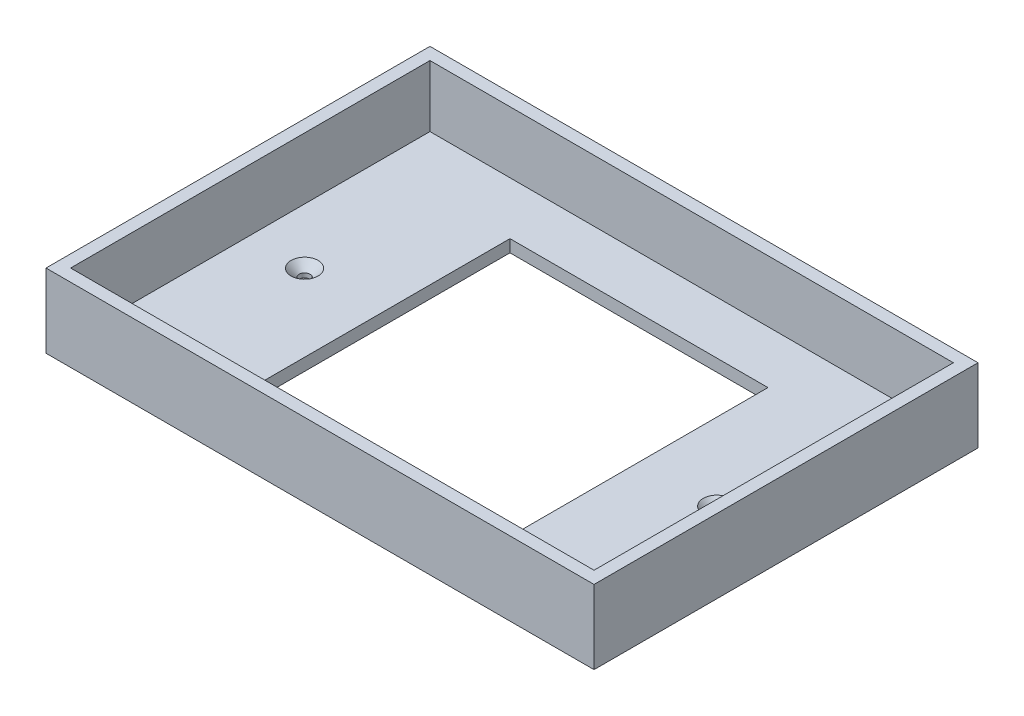
SolidWorks part; units mm, degrees
ref_plane "Front Plane" through (0, 0, 0) normal (0, 0, 1) x (1, 0, 0)
ref_plane "Top Plane" through (0, 0, 0) normal (0, 1, 0) x (1, 0, 0)
ref_plane "Right Plane" through (0, 0, 0) normal (1, 0, 0) x (0, 0, -1)
sketch "Sketch1" plane through (0, 0, 0) normal (0, 1, 0) x (1, 0, 0)
  line L0 (-44.545, -31.21) -> (-44.545, 31.21)
  line L1 (-42.545, -29.21) -> (42.545, -29.21)
  line L2 (-42.545, -29.21) -> (-42.545, 29.21)
  line L3 (-42.545, 29.21) -> (42.545, 29.21)
  line L4 (42.545, -29.21) -> (42.545, 29.21)
  line L5 (-42.545, -29.21) -> (42.545, 29.21) construction
  line L6 (-42.545, 29.21) -> (42.545, -29.21) construction
  line L7 (-44.545, 31.21) -> (44.545, 31.21)
  line L8 (44.545, -31.21) -> (44.545, 31.21)
  line L9 (-44.545, -31.21) -> (44.545, -31.21)
  point P0 (0, 0)
  dimension "D1" = 58.42
  dimension "D2" = 85.09
  dimension "D3" = 2
extrude "Boss-Extrude1" add sketch "Sketch1" against normal blind 2 contours L1 L4 L3 L2 | L0 L9 L8 L7 L4 L1 L2 L3 region at (-43.4572, 0, 0) region at (0, 0, 0)
extrude "Boss-Extrude2" add sketch "Sketch1<3>" along normal blind 10
sketch "Sketch1<3>" plane through (0, 0, 0) normal (0, 1, 0) x (1, 0, 0) same geometry as "Sketch1"
hole_wizard "CSK for M2 Flat Head Machine Screw1" positions "Sketch4" profile "Sketch6" countersink size "M2" standard "ANSI Metric"
sketch "Sketch4" plane through (0, 0, 0) normal (0, 1, 0) x (1, 0, 0)
  circle A0 centre (-33.5, -0.2189) radius 0.8 construction
  circle A1 centre (33.5, -0.2189) radius 0.8 construction
  point P156 (-33.5, -0.2189)
  point P158 (33.5, -0.2189)
  point P161 (0, 0)
  point P164 (0, 0)
sketch "Sketch6" plane through (-33.5, 0, 0.2189) normal (1, 0, 0) x (0, 0, 1)
  line L0 (0, 0) -> (0, 10.4468)
  line L1 (0, 10.4468) -> (0.9, 9.906)
  line L2 (0.9, 9.906) -> (0.9, 1.3)
  line L3 (0.9, 1.3) -> (2.2, 0)
  line L5 (2.2, 0) -> (0, 0)
  line L6 (-0.9, 1.3) -> (-2.2, 0) construction
  line L10 (0, 10.4468) -> (-0.9, 9.906) construction
  line L11 (0, -6.35) -> (0, 107.95) construction
  dimension "Hole Dia." = 1.8
  dimension "Hole Depth" = 9.906
  dimension "Near C'Sink Dia." = 4.4
  dimension "Near C'Sink Angle" = 90
  dimension "Drill Angle" = 118
sketch "Sketch7" plane through (0, 0, 0) normal (0, 1, 0) x (1, 0, 0)
  line L1 (-20.9676, -20.6397) -> (20.9676, -20.6397)
  line L2 (-20.9676, -20.6397) -> (-20.9676, 20.6397)
  line L3 (-20.9676, 20.6397) -> (20.9676, 20.6397)
  line L4 (20.9676, -20.6397) -> (20.9676, 20.6397)
  line L5 (-20.9676, -20.6397) -> (20.9676, 20.6397) construction
  line L6 (-20.9676, 20.6397) -> (20.9676, -20.6397) construction
  point P0 (0, 0)
extrude "Cut-Extrude1" cut sketch "Sketch7" against normal blind 2.54
